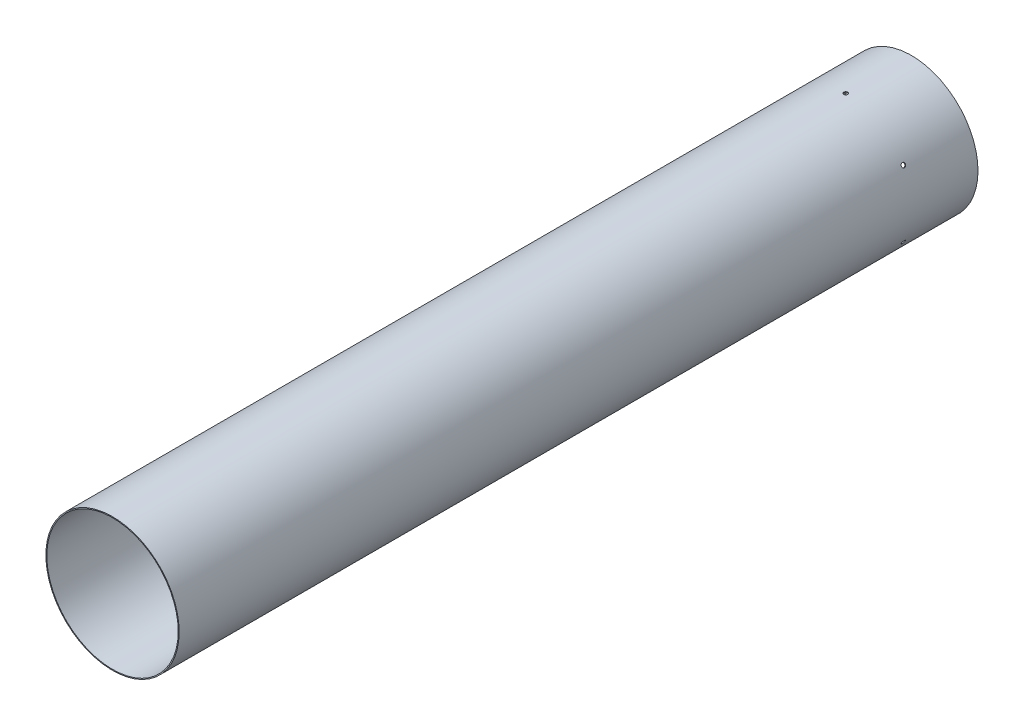
SolidWorks part; units mm, degrees
ref_plane "Front Plane" through (0, 0, 0) normal (0, 0, 1) x (1, 0, 0)
ref_plane "Top Plane" through (0, 0, 0) normal (0, 1, 0) x (1, 0, 0)
ref_plane "Right Plane" through (0, 0, 0) normal (1, 0, 0) x (0, 0, -1)
sketch "Sketch1" plane through (0, 0, 0) normal (0, 0, 1) x (1, 0, 0)
  circle A0 centre (0, 0) radius 79.375
  circle A1 centre (0, 0) radius 80.518
  dimension "D1" = 158.75
  dimension "D2" = 1.143
extrude "Boss-Extrude1" add sketch "Sketch1" along normal blind 965.2
ref_plane "Plane1" through (0, 80.518, 0) normal (0, 1, 0) x (1, 0, 0)
sketch "Sketch2" plane through (0, 80.518, 0) normal (0, 1, 0) x (1, 0, 0)
  line L0 (79.375, 0) -> (-79.375, 0) construction
  point P0 (0, -79.375)
  dimension "D1" = 79.375
hole_wizard "#10 (0.1935) Diameter Hole1" positions "Sketch3" profile "Sketch4" hole size "#10" standard "ANSI Inch" end condition up to next
sketch "Sketch3" plane through (0, 80.518, 0) normal (0, 1, 0) x (1, 0, 0)
  point P0 (0, -79.375)
sketch "Sketch4" plane through (0, 80.518, 79.375) normal (1, 0, 0) x (0, 0, 1)
  line L0 (0, 0) -> (0, 1.143)
  line L1 (0, 1.143) -> (2.4574, 1.143)
  line L2 (2.4574, 1.143) -> (2.4574, 0)
  line L5 (2.4574, 0) -> (0, 0)
  line L11 (0, -6.35) -> (0, 107.95) construction
  dimension "Thru Hole Dia." = 4.9149
  dimension "Thru Hole Depth" = 1.143
pattern_circular "CirPattern1" count 6 over 360 about axis through (0, 0, 0) along (0, 0, 1) of "#10 (0.1935) Diameter Hole1"
